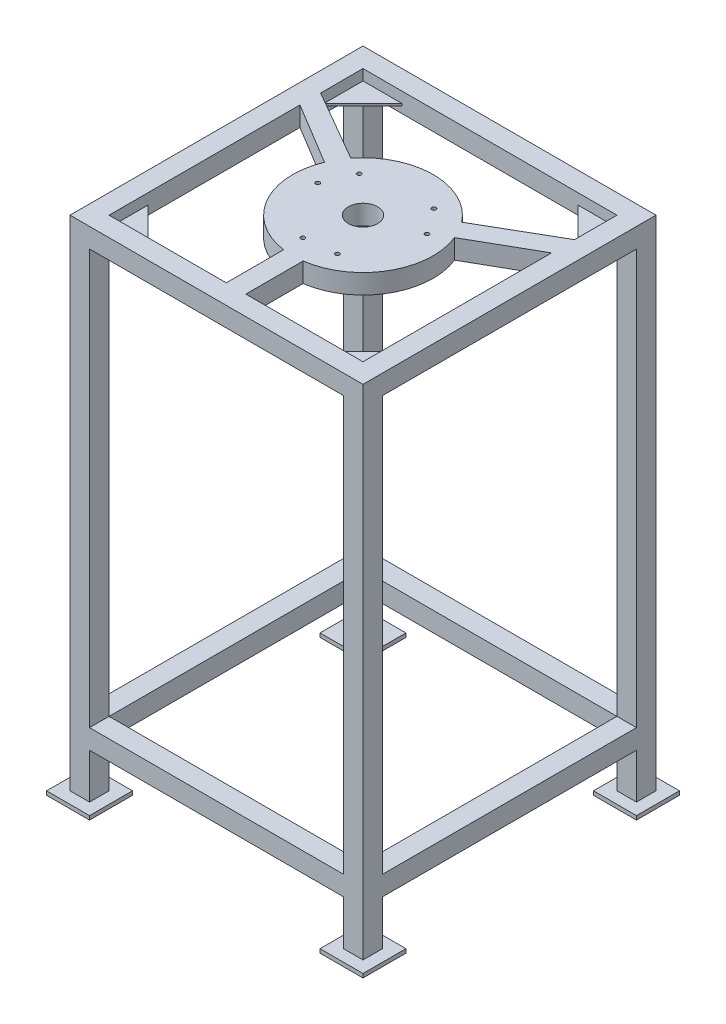
SolidWorks part; units mm, degrees
other "Col2"
other "Col1"
other "Foot4"
other "Foot3"
other "Foot2"
other "Foot1"
other "RingW"
other "RingE"
other "RingN"
other "RingS"
other "Col4"
other "Col3"
other "Brace4"
other "Brace2"
other "Brace1"
other "SupportPlate"
other "BottomRingN"
other "BottomRingS"
other "SpokeC"
other "SpokeB"
other "SpokeA"
other "BottomRingW"
other "BottomRingE"
material "ASTM A36 Steel"
ref_plane "Front Plane" through (0, 0, 0) normal (0, 0, 1) x (1, 0, 0)
ref_plane "Top Plane" through (0, 0, 0) normal (0, 1, 0) x (1, 0, 0)
ref_plane "Right Plane" through (0, 0, 0) normal (1, 0, 0) x (0, 0, -1)
sketch "Sketch1" plane through (0, 0, 0) normal (0, 1, 0) x (1, 0, 0)
  line L1 (0, 0) -> (100, 0)
  line L2 (0, 0) -> (0, 50)
  line L3 (0, 50) -> (100, 50)
  line L4 (100, 0) -> (100, 50)
sketch "Sketch2" plane through (0, 0, 0) normal (0, 1, 0) x (1, 0, 0)
  line L1 (-878.3308, 233.0375) -> (-658.3308, 233.0375)
  line L2 (-878.3308, 233.0375) -> (-878.3308, 453.0375)
  line L3 (-878.3308, 453.0375) -> (-658.3308, 453.0375)
  line L4 (-658.3308, 233.0375) -> (-658.3308, 453.0375)
extrude "Boss-Extrude2" add sketch "Sketch2" along normal blind 20 from offset 2650 offset against normal yes
sketch "Sketch3" plane through (0, 0, 0) normal (0, 1, 0) x (1, 0, 0)
  line L1 (521.6692, 233.0375) -> (741.6692, 233.0375)
  line L2 (521.6692, 233.0375) -> (521.6692, 453.0375)
  line L3 (521.6692, 453.0375) -> (741.6692, 453.0375)
  line L4 (741.6692, 233.0375) -> (741.6692, 453.0375)
extrude "Boss-Extrude3" add sketch "Sketch3" along normal blind 20 from offset 2650 separate body offset against normal yes
sketch "Sketch4" plane through (0, 0, 0) normal (0, 1, 0) x (1, 0, 0)
  line L1 (521.6692, 1633.0375) -> (741.6692, 1633.0375)
  line L2 (521.6692, 1633.0375) -> (521.6692, 1853.0375)
  line L3 (521.6692, 1853.0375) -> (741.6692, 1853.0375)
  line L4 (741.6692, 1633.0375) -> (741.6692, 1853.0375)
extrude "Boss-Extrude4" add sketch "Sketch4" along normal blind 20 from offset 2650 separate body offset against normal yes
sketch "Sketch5" plane through (0, 0, 0) normal (0, 1, 0) x (1, 0, 0)
  line L1 (-878.3308, 1633.0375) -> (-658.3308, 1633.0375)
  line L2 (-878.3308, 1633.0375) -> (-878.3308, 1853.0375)
  line L3 (-878.3308, 1853.0375) -> (-658.3308, 1853.0375)
  line L4 (-658.3308, 1633.0375) -> (-658.3308, 1853.0375)
extrude "Boss-Extrude5" add sketch "Sketch5" along normal blind 20 from offset 2650 separate body offset against normal yes
sketch "Sketch6" plane through (0, 0, 0) normal (0, 1, 0) x (1, 0, 0)
  line L1 (-818.3308, 293.0375) -> (-718.3308, 293.0375)
  line L2 (-818.3308, 293.0375) -> (-818.3308, 393.0375)
  line L3 (-818.3308, 393.0375) -> (-718.3308, 393.0375)
  line L4 (-718.3308, 293.0375) -> (-718.3308, 393.0375)
extrude "Boss-Extrude6" add sketch "Sketch6" along normal blind 2552.2 from offset 2630 separate body offset against normal yes
sketch "Sketch7" plane through (0, 0, 0) normal (0, 1, 0) x (1, 0, 0)
  line L1 (581.6692, 293.0375) -> (681.6692, 293.0375)
  line L2 (581.6692, 293.0375) -> (581.6692, 393.0375)
  line L3 (581.6692, 393.0375) -> (681.6692, 393.0375)
  line L4 (681.6692, 293.0375) -> (681.6692, 393.0375)
extrude "Boss-Extrude7" add sketch "Sketch7" along normal blind 2552.2 from offset 2630 separate body offset against normal yes
sketch "Sketch8" plane through (0, 0, 0) normal (0, 1, 0) x (1, 0, 0)
  line L1 (581.6692, 1693.0375) -> (681.6692, 1693.0375)
  line L2 (581.6692, 1693.0375) -> (581.6692, 1793.0375)
  line L3 (581.6692, 1793.0375) -> (681.6692, 1793.0375)
  line L4 (681.6692, 1693.0375) -> (681.6692, 1793.0375)
extrude "Boss-Extrude8" add sketch "Sketch8" along normal blind 2552.2 from offset 2630 separate body offset against normal yes
sketch "Sketch9" plane through (0, 0, 0) normal (0, 1, 0) x (1, 0, 0)
  line L1 (-818.3308, 1693.0375) -> (-718.3308, 1693.0375)
  line L2 (-818.3308, 1693.0375) -> (-818.3308, 1793.0375)
  line L3 (-818.3308, 1793.0375) -> (-718.3308, 1793.0375)
  line L4 (-718.3308, 1693.0375) -> (-718.3308, 1793.0375)
extrude "Boss-Extrude9" add sketch "Sketch9" along normal blind 2552.2 from offset 2630 separate body offset against normal yes
sketch "Sketch10" plane through (0, 0, 0) normal (0, 1, 0) x (1, 0, 0)
  line L0 (-818.3308, 293.0375) -> (-718.3308, 293.0375) construction
  line L1 (-768.3308, 293.0375) -> (631.6692, 293.0375)
  line L2 (-768.3308, 293.0375) -> (-768.3308, 393.0375)
  line L3 (-768.3308, 393.0375) -> (631.6692, 393.0375)
  line L4 (631.6692, 293.0375) -> (631.6692, 393.0375)
extrude "Boss-Extrude10" add sketch "Sketch10" along normal blind 100 from offset 177.8 separate body offset against normal yes
sketch "Sketch11" plane through (0, 0, 0) normal (0, 1, 0) x (1, 0, 0)
  line L0 (-818.3308, 1693.0375) -> (-718.3308, 1693.0375) construction
  line L1 (-768.3308, 1693.0375) -> (631.6692, 1693.0375)
  line L2 (-768.3308, 1693.0375) -> (-768.3308, 1793.0375)
  line L3 (-768.3308, 1793.0375) -> (631.6692, 1793.0375)
  line L4 (631.6692, 1693.0375) -> (631.6692, 1793.0375)
extrude "Boss-Extrude11" add sketch "Sketch11" along normal blind 100 from offset 177.8 separate body offset against normal yes
sketch "Sketch12" plane through (0, 0, 0) normal (0, 1, 0) x (1, 0, 0)
  line L0 (681.6692, 1693.0375) -> (681.6692, 1793.0375) construction
  line L1 (581.6692, 343.0375) -> (681.6692, 343.0375)
  line L2 (581.6692, 343.0375) -> (581.6692, 1743.0375)
  line L3 (581.6692, 1743.0375) -> (681.6692, 1743.0375)
  line L4 (681.6692, 343.0375) -> (681.6692, 1743.0375)
extrude "Boss-Extrude12" add sketch "Sketch12" along normal blind 100 from offset 177.8 separate body offset against normal yes
sketch "Sketch13" plane through (0, 0, 0) normal (0, 1, 0) x (1, 0, 0)
  line L0 (-718.3308, 1693.0375) -> (-718.3308, 1793.0375) construction
  line L1 (-818.3308, 343.0375) -> (-718.3308, 343.0375)
  line L2 (-818.3308, 343.0375) -> (-818.3308, 1743.0375)
  line L3 (-818.3308, 1743.0375) -> (-718.3308, 1743.0375)
  line L4 (-718.3308, 343.0375) -> (-718.3308, 1743.0375)
extrude "Boss-Extrude13" add sketch "Sketch13" along normal blind 100 from offset 177.8 separate body offset against normal yes
sketch "Sketch14" plane through (0, 0, 0) normal (0, 1, 0) x (1, 0, 0)
  line L1 (-768.3308, 793.0375) -> (631.6692, 793.0375)
  line L2 (-768.3308, 793.0375) -> (-768.3308, 893.0375)
  line L3 (-768.3308, 893.0375) -> (631.6692, 893.0375)
  line L4 (631.6692, 793.0375) -> (631.6692, 893.0375)
sketch "Sketch15" plane through (0, 0, 0) normal (0, 1, 0) x (1, 0, 0)
  line L1 (-768.3308, 1193.0375) -> (631.6692, 1193.0375)
  line L2 (-768.3308, 1193.0375) -> (-768.3308, 1293.0375)
  line L3 (-768.3308, 1293.0375) -> (631.6692, 1293.0375)
  line L4 (631.6692, 1193.0375) -> (631.6692, 1293.0375)
sketch "Sketch41" plane through (0, 0, 0) normal (0, 1, 0) x (1, 0, 0)
  line L1 (-813.3308, 298.0375) -> (-723.3308, 298.0375)
  line L2 (-813.3308, 298.0375) -> (-813.3308, 388.0375)
  line L3 (-813.3308, 388.0375) -> (-723.3308, 388.0375)
  line L4 (-723.3308, 298.0375) -> (-723.3308, 388.0375)
  line L5 (586.6692, 298.0375) -> (676.6692, 298.0375)
  line L6 (586.6692, 298.0375) -> (586.6692, 388.0375)
  line L7 (586.6692, 388.0375) -> (676.6692, 388.0375)
  line L8 (676.6692, 298.0375) -> (676.6692, 388.0375)
  line L9 (586.6692, 1698.0375) -> (676.6692, 1698.0375)
  line L10 (586.6692, 1698.0375) -> (586.6692, 1788.0375)
  line L11 (586.6692, 1788.0375) -> (676.6692, 1788.0375)
  line L12 (676.6692, 1698.0375) -> (676.6692, 1788.0375)
  line L13 (-813.3308, 1698.0375) -> (-723.3308, 1698.0375)
  line L14 (-813.3308, 1698.0375) -> (-813.3308, 1788.0375)
  line L15 (-813.3308, 1788.0375) -> (-723.3308, 1788.0375)
  line L16 (-723.3308, 1698.0375) -> (-723.3308, 1788.0375)
extrude "Cut-Extrude9" cut sketch "Sketch41" along normal blind 2452.2 from offset 2630 offset against normal yes
sketch "Sketch43" plane through (0, 0, 0) normal (1, 0, 0) x (0, 0, -1)
  line L1 (298.0375, -172.8) -> (388.0375, -172.8)
  line L2 (298.0375, -172.8) -> (298.0375, -82.8)
  line L3 (298.0375, -82.8) -> (388.0375, -82.8)
  line L4 (388.0375, -172.8) -> (388.0375, -82.8)
  line L5 (1698.0375, -172.8) -> (1788.0375, -172.8)
  line L6 (1698.0375, -172.8) -> (1698.0375, -82.8)
  line L7 (1698.0375, -82.8) -> (1788.0375, -82.8)
  line L8 (1788.0375, -172.8) -> (1788.0375, -82.8)
  line L9 (798.0375, -172.8) -> (888.0375, -172.8)
  line L10 (798.0375, -172.8) -> (798.0375, -82.8)
  line L11 (798.0375, -82.8) -> (888.0375, -82.8)
  line L12 (888.0375, -172.8) -> (888.0375, -82.8)
  line L13 (1198.0375, -172.8) -> (1288.0375, -172.8)
  line L14 (1198.0375, -172.8) -> (1198.0375, -82.8)
  line L15 (1198.0375, -82.8) -> (1288.0375, -82.8)
  line L16 (1288.0375, -172.8) -> (1288.0375, -82.8)
extrude "Cut-Extrude11" cut sketch "Sketch43" along normal blind 1300 from offset 718.3308 offset against normal yes
sketch "Sketch44" plane through (0, 0, 0) normal (0, 0, 1) x (1, 0, 0)
  line L1 (586.6692, -172.8) -> (676.6692, -172.8)
  line L2 (586.6692, -172.8) -> (586.6692, -82.8)
  line L3 (586.6692, -82.8) -> (676.6692, -82.8)
  line L4 (676.6692, -172.8) -> (676.6692, -82.8)
  line L5 (-813.3308, -172.8) -> (-723.3308, -172.8)
  line L6 (-813.3308, -172.8) -> (-813.3308, -82.8)
  line L7 (-813.3308, -82.8) -> (-723.3308, -82.8)
  line L8 (-723.3308, -172.8) -> (-723.3308, -82.8)
extrude "Cut-Extrude12" cut sketch "Sketch44" along normal blind 1300 from offset 1693.0375 offset against normal yes
sketch "Sketch45" plane through (0, 0, 0) normal (0, 1, 0) x (1, 0, 0)
  circle A0 centre (-68.3308, 1043.0375) radius 360
extrude "Boss-Extrude27" add sketch "Sketch45" along normal up to surface (-77.8 mm away) from offset 177.8 separate body up to face at (-768.3308, -77.8, -1043.0375) offset against normal yes
sketch "Sketch46" plane through (0, 0, 0) normal (0, 1, 0) x (1, 0, 0)
  line L0 (-768.3308, 343.0375) -> (-468.3308, 343.0375)
  line L1 (-468.3308, 343.0375) -> (-768.3308, 643.0375)
  line L2 (-768.3308, 643.0375) -> (-768.3308, 343.0375)
extrude "Boss-Extrude28" add sketch "Sketch46" along normal blind 10 from offset 142.8 separate body offset against normal yes
sketch "Sketch47" plane through (0, 0, 0) normal (0, 1, 0) x (1, 0, 0)
  line L0 (631.6692, 343.0375) -> (331.6692, 343.0375)
  line L1 (331.6692, 343.0375) -> (631.6692, 643.0375)
  line L2 (631.6692, 643.0375) -> (631.6692, 343.0375)
extrude "Boss-Extrude29" add sketch "Sketch47" along normal blind 10 from offset 142.8 separate body offset against normal yes
sketch "Sketch48" plane through (0, 0, 0) normal (0, 1, 0) x (1, 0, 0)
  line L0 (631.6692, 1743.0375) -> (331.6692, 1743.0375)
  line L1 (331.6692, 1743.0375) -> (631.6692, 1443.0375)
  line L2 (631.6692, 1443.0375) -> (631.6692, 1743.0375)
extrude "Boss-Extrude30" add sketch "Sketch48" along normal blind 10 from offset 142.8 separate body offset against normal yes
sketch "Sketch49" plane through (0, 0, 0) normal (0, 1, 0) x (1, 0, 0)
  line L0 (-768.3308, 1743.0375) -> (-468.3308, 1743.0375)
  line L1 (-468.3308, 1743.0375) -> (-768.3308, 1443.0375)
  line L2 (-768.3308, 1443.0375) -> (-768.3308, 1743.0375)
extrude "Boss-Extrude31" add sketch "Sketch49" along normal blind 10 from offset 142.8 separate body offset against normal yes
sketch "Sketch50" plane through (0, 0, 0) normal (0, 1, 0) x (1, 0, 0)
  circle A0 centre (-68.3308, 1043.0375) radius 75
  circle A1 centre (-261.8518, 1216.674) radius 10.5
  circle A2 centre (37.8351, 805.7006) radius 10.5
  circle A3 centre (-326.9535, 1069.7636) radius 10.5
  circle A4 centre (178.8033, 1123.8134) radius 10.5
  circle A5 centre (84.126, 1253.6483) radius 10.5
  circle A6 centre (-121.9439, 788.6252) radius 10.5
extrude "Cut-Extrude13" cut sketch "Sketch50" along normal through all from offset 177.8 offset against normal yes
sketch "Sketch57" plane through (0, 0, 0) normal (0, 1, 0) x (1, 0, 0)
  line L0 (166.4768, 1236.3388) -> (216.4768, 1149.7362)
  line L1 (216.4768, 1149.7362) -> (656.6472, 1401.3394)
  line L2 (656.6472, 1401.3394) -> (656.6472, 1519.3388)
  line L3 (656.6472, 1519.3388) -> (166.4768, 1236.3388)
extrude "Boss-Extrude36" add sketch "Sketch57" along normal blind 100 from offset 177.8 separate body offset against normal yes
sketch "Sketch58" plane through (0, 0, 0) normal (0, 1, 0) x (1, 0, 0)
  line L0 (-353.1384, 1149.7362) -> (-303.1384, 1236.3388)
  line L1 (-303.1384, 1236.3388) -> (-793.3088, 1519.3388)
  line L2 (-793.3088, 1519.3388) -> (-802.7801, 1421.2928)
  line L3 (-802.7801, 1421.2928) -> (-353.1384, 1149.7362)
extrude "Boss-Extrude37" add sketch "Sketch58" along normal blind 100 from offset 177.8 separate body offset against normal yes
sketch "Sketch59" plane through (0, 0, 0) normal (0, 1, 0) x (1, 0, 0)
  line L0 (-18.3308, 743.0375) -> (-118.3308, 743.0375)
  line L1 (-118.3308, 743.0375) -> (-118.3308, 293.0375)
  line L2 (-118.3308, 293.0375) -> (-18.3308, 293.0375)
  line L3 (-18.3308, 293.0375) -> (-18.3308, 743.0375)
extrude "Boss-Extrude38" add sketch "Sketch59" along normal blind 100 from offset 177.8 separate body offset against normal yes
sketch "Sketch60" plane through (0, 0, 0) normal (0, 1, 0) x (1, 0, 0)
  line L0 (246.9191, 1277.0086) -> (291.9191, 1199.0664)
  line L1 (291.9191, 1199.0664) -> (586.3677, 1369.0664)
  line L2 (586.3677, 1369.0664) -> (541.3677, 1447.0086)
  line L3 (541.3677, 1447.0086) -> (246.9191, 1277.0086)
  line L4 (-428.5807, 1199.0664) -> (-383.5807, 1277.0086)
  line L5 (-383.5807, 1277.0086) -> (-678.0293, 1447.0086)
  line L6 (-678.0293, 1447.0086) -> (-723.0293, 1369.0664)
  line L7 (-723.0293, 1369.0664) -> (-428.5807, 1199.0664)
  line L8 (-23.3308, 693.0375) -> (-113.3308, 693.0375)
  line L9 (-113.3308, 693.0375) -> (-113.3308, 413.0375)
  line L10 (-113.3308, 413.0375) -> (-23.3308, 413.0375)
  line L11 (-23.3308, 413.0375) -> (-23.3308, 693.0375)
sketch "Sketch61" plane through (0, 0, 0) normal (0, 1, 0) x (1, 0, 0)
  line L1 (-768.3308, 293.0375) -> (631.6692, 293.0375)
  line L2 (-768.3308, 293.0375) -> (-768.3308, 393.0375)
  line L3 (-768.3308, 393.0375) -> (631.6692, 393.0375)
  line L4 (631.6692, 293.0375) -> (631.6692, 393.0375)
extrude "Boss-Extrude39" add sketch "Sketch61" along normal blind 100 from offset 2400 separate body offset against normal yes
sketch "Sketch62" plane through (0, 0, 0) normal (0, 1, 0) x (1, 0, 0)
  line L1 (-768.3308, 1693.0375) -> (631.6692, 1693.0375)
  line L2 (-768.3308, 1693.0375) -> (-768.3308, 1793.0375)
  line L3 (-768.3308, 1793.0375) -> (631.6692, 1793.0375)
  line L4 (631.6692, 1693.0375) -> (631.6692, 1793.0375)
extrude "Boss-Extrude40" add sketch "Sketch62" along normal blind 100 from offset 2400 separate body offset against normal yes
sketch "Sketch63" plane through (0, 0, 0) normal (0, 1, 0) x (1, 0, 0)
  line L1 (581.6692, 343.0375) -> (681.6692, 343.0375)
  line L2 (581.6692, 343.0375) -> (581.6692, 1743.0375)
  line L3 (581.6692, 1743.0375) -> (681.6692, 1743.0375)
  line L4 (681.6692, 343.0375) -> (681.6692, 1743.0375)
extrude "Boss-Extrude41" add sketch "Sketch63" along normal blind 100 from offset 2400 separate body offset against normal yes
sketch "Sketch64" plane through (0, 0, 0) normal (0, 1, 0) x (1, 0, 0)
  line L1 (-818.3308, 343.0375) -> (-718.3308, 343.0375)
  line L2 (-818.3308, 343.0375) -> (-818.3308, 1743.0375)
  line L3 (-818.3308, 1743.0375) -> (-718.3308, 1743.0375)
  line L4 (-718.3308, 343.0375) -> (-718.3308, 1743.0375)
extrude "Boss-Extrude42" add sketch "Sketch64" along normal blind 100 from offset 2400 separate body offset against normal yes
sketch "Sketch65" plane through (0, 0, 0) normal (1, 0, 0) x (0, 0, -1)
  line L1 (298.0375, -2395) -> (388.0375, -2395)
  line L2 (298.0375, -2395) -> (298.0375, -2305)
  line L3 (298.0375, -2305) -> (388.0375, -2305)
  line L4 (388.0375, -2395) -> (388.0375, -2305)
  line L5 (1698.0375, -2395) -> (1788.0375, -2395)
  line L6 (1698.0375, -2395) -> (1698.0375, -2305)
  line L7 (1698.0375, -2305) -> (1788.0375, -2305)
  line L8 (1788.0375, -2395) -> (1788.0375, -2305)
extrude "Cut-Extrude17" cut sketch "Sketch65" along normal blind 1300 from offset 718.3308 offset against normal yes
sketch "Sketch66" plane through (0, 0, 0) normal (0, 0, 1) x (1, 0, 0)
  line L1 (586.6692, -2395) -> (676.6692, -2395)
  line L2 (586.6692, -2395) -> (586.6692, -2305)
  line L3 (586.6692, -2305) -> (676.6692, -2305)
  line L4 (676.6692, -2395) -> (676.6692, -2305)
  line L5 (-813.3308, -2395) -> (-723.3308, -2395)
  line L6 (-813.3308, -2395) -> (-813.3308, -2305)
  line L7 (-813.3308, -2305) -> (-723.3308, -2305)
  line L8 (-723.3308, -2395) -> (-723.3308, -2305)
extrude "Cut-Extrude18" cut sketch "Sketch66" along normal blind 1300 from offset 1693.0375 offset against normal yes
combine bodies "Combine3" operation type add bodies to combine 191 183 192 141 140 229 139 228 198 227 226 215 197 138 214 196 213 186 187 185 199 188 184
combine bodies "Combine4" operation type add bodies to combine 202 230
